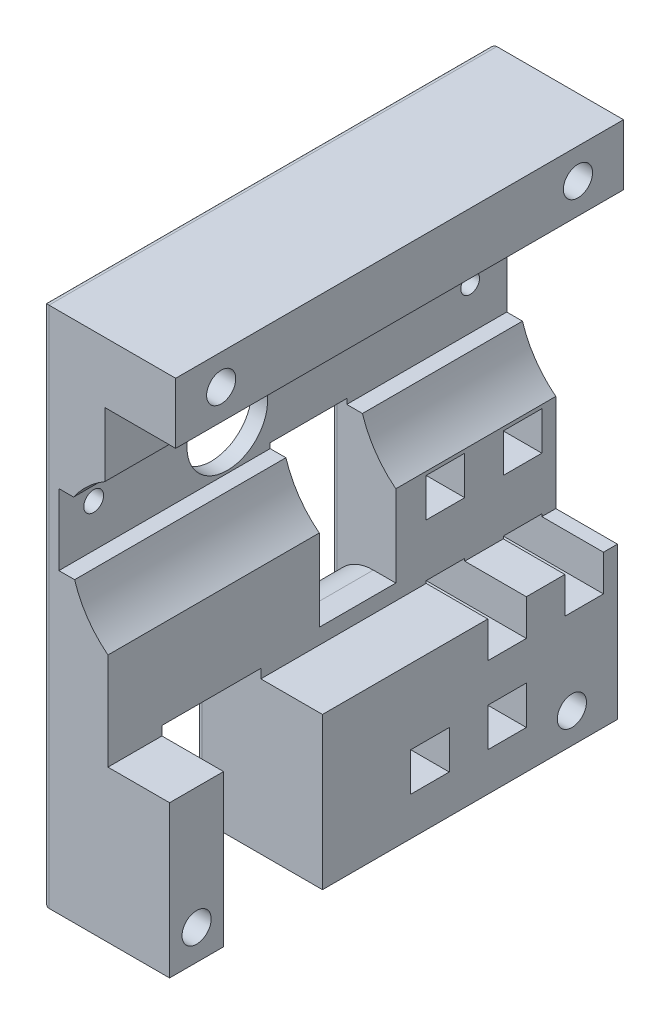
SolidWorks part; units mm, degrees
ref_plane "Front" through (0, 0, 0) normal (0, 0, 1) x (1, 0, 0)
ref_plane "Top" through (0, 0, 0) normal (0, 1, 0) x (1, 0, 0)
ref_plane "Right" through (0, 0, 0) normal (1, 0, 0) x (0, 0, -1)
sketch "Profile" plane through (0, 0, 0) normal (0, 0, 1) x (1, 0, 0)
  line L0 (9.3013, -54.1947) -> (9.3013, -29.1947)
  line L1 (-11.5587, -54.1947) -> (9.3013, -54.1947)
  line L2 (-11.5587, -54.1947) -> (-11.5587, 31.8453)
  line L3 (-11.5587, 31.8453) -> (10.3013, 31.8453)
  line L4 (10.3013, 21.8453) -> (10.3013, 31.8453)
  line L7 (9.3013, -29.1947) -> (-0.8487, -29.1947)
  line L8 (-0.8487, -29.1947) -> (-0.8487, -13.1966)
  line L10 (10.3013, 21.8453) -> (-1.3487, 21.8453)
  line L11 (-1.3487, 21.8453) -> (-1.3487, 11.2835)
  line L12 (-6.5097, 6.4953) -> (-8.9287, 6.4953)
  line L13 (-8.9287, 6.4953) -> (-8.9287, -5.2047)
  line L14 (-8.9287, -5.2047) -> (-6.3407, -5.2047)
  arc A0 (-6.3407, -5.2047) -> (-0.8487, -13.1966) centre (9.1973, -0.41) ccw
  arc A1 (-6.5097, 6.4953) -> (-1.3487, 11.2835) centre (6.8684, -2.7485) cw
  point P0 (0, 0)
  dimension "D15" = 16.261
  dimension "D16" = 16.261
  dimension "D1" = 86.04
  dimension "D2" = 21.86
  dimension "D3" = 10
  dimension "D4" = 25
  dimension "D5" = 20.86
  dimension "D6" = 10.15
  dimension "D7" = 11.65
  dimension "D8" = 10.5617
  dimension "D9" = 15.9981
  dimension "D10" = 2.588
  dimension "D11" = 11.7
  dimension "D12" = 2.4191
  dimension "D13" = 5.492
  dimension "D14" = 23.99
extrude "ProfileExtrude" add sketch "Profile" along normal blind 73.76
sketch "HoseWindow" plane through (-11.5587, 0, 0) normal (-1, 0, 0) x (0, 0, 1)
  line L0 (73.76, -54.1947) -> (0, -54.1947) construction
  line L1 (64.87, -54.1947) -> (48.58, -54.1947)
  line L2 (64.87, -54.1947) -> (64.87, -27.6947)
  line L3 (64.87, -27.6947) -> (48.58, -27.6947)
  line L4 (48.58, -54.1947) -> (48.58, -27.6947)
  dimension "D1" = 16.29
  dimension "D2" = 26.5
  dimension "D3" = 8.89
extrude "HoseWindowCut" cut sketch "HoseWindow" against normal through all
sketch "CageScrews" plane through (-11.5587, 0, 0) normal (-1, 0, 0) x (0, 0, 1)
  line L0 (73.76, 31.8453) -> (0, 31.8453) construction
  line L1 (0, 31.8453) -> (0, -54.1947) construction
  line L2 (73.76, 31.8453) -> (73.76, -54.1947) construction
  line L3 (73.76, -54.1947) -> (64.87, -54.1947) construction
  line L4 (48.58, -54.1947) -> (0, -54.1947) construction
  circle A0 centre (7.5, 26.8453) radius 2.4
  circle A1 centre (66.26, 26.8453) radius 2.4
  circle A2 centre (7.5, -49.1947) radius 2.4
  circle A3 centre (69.31, -49.1947) radius 2.4
  dimension "D1" = 4.8
  dimension "D2" = 5
  dimension "D3" = 7.5
  dimension "D4" = 7.5
  dimension "D5" = 5
  dimension "D6" = 5
  dimension "D7" = 4.45
  dimension "D8" = 5
  dimension "D9" = 7.5
extrude "CageScrewsCut" cut sketch "CageScrews" against normal through all
sketch "AxleHole" plane through (-11.5587, 0, 0) normal (-1, 0, 0) x (0, 0, 1)
  line L0 (46.03, -4.7837) -> (46.03, 6.7405) construction
  line L1 (47.361, 8.3595) -> (47.361, 6.7405)
  line L2 (47.361, 6.7405) -> (44.699, 6.7405)
  line L3 (44.699, 6.7405) -> (44.699, 8.3595)
  line L5 (48.58, -54.1947) -> (0, -54.1947) construction
  line L6 (0, 31.8453) -> (0, -54.1947) construction
  line L7 (39.391, 1.8553) -> (52.669, 1.8553) construction
  arc A0 (44.699, 8.3595) -> (47.361, 8.3595) centre (46.03, 1.8553) ccw
  dimension "D1" = 13.278
  dimension "D2" = 1.331
  dimension "D3" = 1.619
  dimension "D4" = 1.619
  dimension "D5" = 46.03
  dimension "D6" = 56.05
extrude "AxleHoleCut" cut sketch "AxleHole" against normal through all
sketch "SetScrewHoles" plane through (-11.5587, 0, 0) normal (-1, 0, 0) x (0, 0, 1)
  line L0 (47.361, 6.7405) -> (44.699, 6.7405) construction
  circle A0 centre (6.03, 1.8553) radius 1.5394
  circle A1 centre (68.03, 1.8553) radius 1.629
  point P6 (46.03, 6.7405)
  point P7 (46.03, 6.7405)
  dimension "D1" = 22
  dimension "D2" = 40
extrude "SetScrewHolesCut" cut sketch "SetScrewHoles" against normal through all
sketch "VelocityWindow" plane through (-11.5587, 0, 0) normal (-1, 0, 0) x (0, 0, 1)
  line L0 (73.76, 31.8453) -> (73.76, -54.1947) construction
  line L1 (38.96, -26.6447) -> (26.35, -26.6447)
  line L2 (38.96, -26.6447) -> (38.96, -4.3547)
  line L3 (38.96, -4.3547) -> (26.35, -4.3547)
  line L4 (26.35, -26.6447) -> (26.35, -4.3547)
  line L5 (38.96, -26.6447) -> (26.35, -4.3547) construction
  line L6 (38.96, -4.3547) -> (26.35, -26.6447) construction
  line L7 (48.58, -54.1947) -> (0, -54.1947) construction
  point P0 (32.655, -15.4997)
  dimension "D1" = 12.61
  dimension "D2" = 22.29
  dimension "D3" = 34.8
  dimension "D4" = 27.55
extrude "VelocityWindowCut" cut sketch "VelocityWindow" against normal through all
fillet "Fillet3" radius 7 1 edges at (-11.5587, -26.6447, 32.655)
sketch "TriggerRackSlotCut" plane through (-11.5587, 0, 0) normal (-1, 0, 0) x (0, 0, 1)
  line L0 (15, -41.4947) -> (21.35, -41.4947)
  line L1 (15, -41.4947) -> (15, -47.8447)
  line L2 (21.35, -41.4947) -> (21.35, -47.8447)
  line L3 (15, -47.8447) -> (21.35, -47.8447)
  line L4 (0, 31.8453) -> (0, -54.1947) construction
  line L5 (27.7, -41.4947) -> (34.05, -41.4947)
  line L6 (34.05, -41.4947) -> (34.05, -47.8447)
  line L7 (27.7, -47.8447) -> (34.05, -47.8447)
  line L8 (27.7, -41.4947) -> (27.7, -47.8447)
  line L9 (8.65, -28.7947) -> (8.65, -35.1447)
  line L10 (2.3, -28.7947) -> (8.65, -28.7947)
  line L11 (2.3, -28.7947) -> (2.3, -35.1447)
  line L12 (2.3, -35.1447) -> (8.65, -35.1447)
  line L13 (15, -28.7947) -> (21.35, -28.7947)
  line L14 (21.35, -28.7947) -> (21.35, -35.1447)
  line L15 (15, -35.1447) -> (21.35, -35.1447)
  line L16 (48.58, -54.1947) -> (0, -54.1947) construction
  line L17 (15, -28.7947) -> (15, -35.1447)
  line L18 (15, -41.4947) -> (15, -28.7947) construction
  line L19 (27.7, -28.7947) -> (34.05, -28.7947) [skipped]
  line L20 (34.05, -28.7947) -> (34.05, -35.1447) [skipped]
  line L21 (27.7, -35.1447) -> (34.05, -35.1447) [skipped]
  line L22 (27.7, -28.7947) -> (27.7, -35.1447) [skipped]
  line L23 (8.65, -13.7947) -> (8.65, -20.1447)
  line L24 (2.3, -13.7947) -> (8.65, -13.7947)
  line L25 (2.3, -13.7947) -> (2.3, -20.1447)
  line L26 (2.3, -20.1447) -> (8.65, -20.1447)
  line L27 (15, -13.7947) -> (21.35, -13.7947)
  line L28 (21.35, -13.7947) -> (21.35, -20.1447)
  line L29 (15, -20.1447) -> (21.35, -20.1447)
  line L30 (15, -13.7947) -> (15, -20.1447)
  dimension "D1" = 6.35
  dimension "D2" = 15
  dimension "D3" = 6.35
  dimension "D4" = 6.35
  dimension "D7" = 12.7
  dimension "D5" = 2
  dimension "D6" = 2
  dimension "D8" = 2
  dimension "D9" = 2
extrude "RackSlotCut" cut sketch "TriggerRackSlotCut" against normal through all
fillet "Fillet4" radius 1 35 edges at (-11.5587, -16.9697, 15) (-11.5587, -20.1447, 18.175) (-11.5587, -16.9697, 21.35) (-11.5587, -13.7947, 18.175) (-11.5587, -13.7947, 5.475) (-11.5587, -16.9697, 2.3) (-11.5587, -16.9697, 8.65) (-11.5587, -20.1447, 5.475) (-11.5587, -35.1447, 5.475) (-11.5587, -31.9697, 2.3) (-11.5587, -28.7947, 5.475) (-11.5587, -31.9697, 8.65) (-11.5587, -31.9697, 21.35) (-11.5587, -28.7947, 18.175) (-11.5587, -31.9697, 15) (-11.5587, -35.1447, 18.175) (-11.5587, -47.8447, 18.175) (-11.5587, -44.6697, 15) (-11.5587, -41.4947, 18.175) (-11.5587, -44.6697, 21.35) (-11.5587, -44.6697, 27.7) (-11.5587, -47.8447, 30.875) (-11.5587, -44.6697, 34.05) (-11.5587, -41.4947, 30.875) (-11.5587, -18.9997, 38.96) (-11.5587, -4.3547, 32.655) (-11.5587, -18.9997, 26.35) (-11.5587, -11.1747, 0) (-11.5587, -54.1947, 24.29) (-11.5587, -40.9447, 48.58) (-11.5587, -27.6947, 56.725) (-11.5587, -40.9447, 64.87) (-11.5587, -54.1947, 69.315) (-11.5587, -11.1747, 73.76) (-11.5587, 31.8453, 36.88)
equation "\"BottomEdge\"=20.86mm"
equation "\"TopEdge\"=21.86mm"
equation "\"TotalHeight\"=86.04mm"
equation "\"TotalLength\"=73.76mm"
equation "\"ScrewClearance\"=10mm"
equation "\"TopDepth\"= 11.65mm"
equation "\"BottomDepth\"=10.15mm"
equation "\"TopHeight\"=10.56175mm"
equation "\"BottomHeight\"=15.99813mm"
equation "\"TopChannelDepth\"=2.41908mm"
equation "\"BottomChannelDepth\"=2.588mm"
equation "\"ChannelHeight\"=11.7mm"
equation "\"ChanRelHeight\"=23.99mm"
equation "\"ChanRelDepth\"=5.492mm"
equation "\"ChamberRadius\"=16.261mm"
equation "\"CageScrewDiameter\"=4.8mm"
equation "\"SetScrewDiameter\"=3.5mm"
equation "\"AxleRadius\"=6.639mm"
equation "\"KeyHeight\"=1.619mm"
equation "\"KeyWidth\"=2.662mm"
equation "\"HoseWindowWidth\"=16.29mm"
equation "\"HoseWindowHeight\"=26.5mm"
equation "\"HoseWindow-Edge\"=8.89mm"
equation "\"CageScrew-VerticalEdge\"=5.0mm"
equation "\"CageScrew-HorizontalEdge\"=7.5mm"
equation "\"CageScrew-HoseCornerScrewEdge\"=4.45mm"
equation "\"Axle-BottomEdge\"=56.05mm"
equation "\"BackSetScrew-Axel\"=40mm"
equation "\"FrontSetScrew-Axel\"=22mm"
equation "\"VelocityWindow-Backedge\"=34.8mm"
equation "\"velocityWindow-bottomedge\"=27.55mm"
equation "\"VelocityWindowHeight\"=22.29mm"
equation "\"VelocityWindowWidth\"=12.61mm"
equation "\"D11@Profile\"= \"ChannelHeight\""
equation "\"D10@Profile\"= \"BottomChannelDepth\""
equation "\"D12@Profile\"= \"TopChannelDepth\""
equation "\"D8@Profile\" = \"TopHeight\""
equation "\"D9@Profile\"= \"BottomHeight\""
equation "\"D6@Profile\"= \"BottomDepth\""
equation "\"D7@Profile\"= \"TopDepth\""
equation "\"D3@Profile\"= \"ScrewClearance\""
equation "\"ScrewClearanceBottom\"=25mm"
equation "\"D4@Profile\"=\"ScrewClearanceBottom\""
equation "\"D5@Profile\"= \"BottomEdge\""
equation "\"D2@Profile\"= \"TopEdge\""
equation "\"D1@Profile\"= \"TotalHeight\""
equation "\"D13@Profile\"= \"ChanRelDepth\""
equation "\"D14@Profile\"= \"ChanRelHeight\""
equation "\"D15@Profile\"= \"ChamberRadius\""
equation "\"D16@Profile\"= \"ChamberRadius\""
equation "\"D1@ProfileExtrude\"= \"TotalLength\""
equation "\"D3@HoseWindow\"= \"HoseWindow-Edge\""
equation "\"D2@HoseWindow\"= \"HoseWindowHeight\""
equation "\"D1@HoseWindow\"= \"HoseWindowWidth\""
equation "\"D1@CageScrews\"= \"CageScrewDiameter\""
equation "\"D9@CageScrews\" = \"CageScrew-HorizontalEdge\""
equation "\"D7@CageScrews\" = \"CageScrew-HoseCornerScrewEdge\""
equation "\"D4@CageScrews\" = \"CageScrew-HorizontalEdge\""
equation "\"D6@CageScrews\"= \"CageScrew-VerticalEdge\""
equation "\"D5@CageScrews\"= \"CageScrew-VerticalEdge\""
equation "\"D8@CageScrews\"= \"CageScrew-VerticalEdge\""
equation "\"D2@CageScrews\"= \"CageScrew-VerticalEdge\""
equation "\"D1@AxleHole\"= \"AxleRadius\" * 2"
equation "\"D4@AxleHole\"= \"KeyHeight\""
equation "\"D3@AxleHole\"= \"KeyHeight\""
equation "\"D2@AxleHole\"= \"KeyWidth\" / 2"
equation "\"Axle-FrontEdge\"=46.03mm"
equation "\"D6@AxleHole\"= \"Axle-BottomEdge\""
equation "\"D5@AxleHole\"= \"Axle-FrontEdge\""
equation "\"D2@SetScrewHoles\"= \"BackSetScrew-Axel\""
equation "\"D1@SetScrewHoles\"= \"FrontSetScrew-Axel\""
equation "\"D1@VelocityWindow\"= \"VelocityWindowWidth\""
equation "\"D2@VelocityWindow\"= \"VelocityWindowHeight\""
equation "\"D3@VelocityWindow\"= \"VelocityWindow-Backedge\""
equation "\"D4@VelocityWindow\"= \"velocityWindow-bottomedge\""
equation "\"bottomslotheight\"=6.35mm"
equation "\"D1@TriggerRackSlotCut\"=\"bottomslotheight\""
equation "\"FrontSlotDepth\"=15mm"
equation "\"SlotSize\"=6.35mm"
equation "\"D3@TriggerRackSlotCut\"=\"SlotSize\""
equation "\"D4@TriggerRackSlotCut\"=\"SlotSize\""
equation "\"D2@TriggerRackSlotCut\"=\"FrontSlotDepth\""
